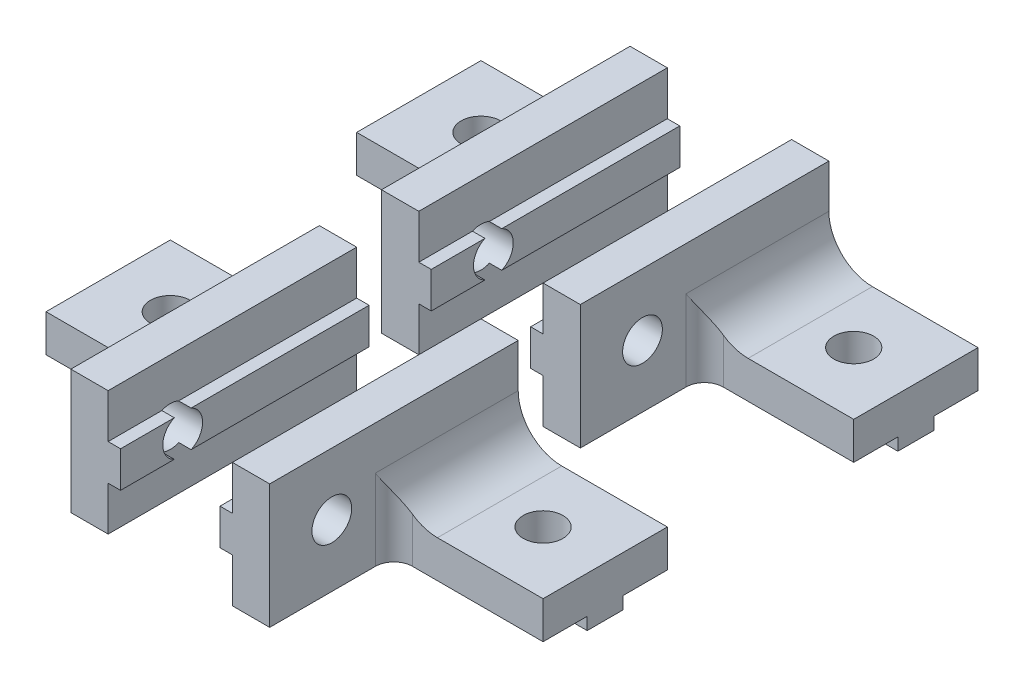
SolidWorks part; units mm, degrees
ref_plane "Front Plane" through (0, 0, 0) normal (0, 0, 1) x (1, 0, 0)
ref_plane "Top Plane" through (0, 0, 0) normal (0, 1, 0) x (1, 0, 0)
ref_plane "Right Plane" through (0, 0, 0) normal (1, 0, 0) x (0, 0, -1)
sketch "Esquisse1" plane through (0, 0, 0) normal (0, 0, 1) x (1, 0, 0)
  line L0 (0, 0) -> (15, 0)
  line L1 (15, 0) -> (15, 3)
  line L2 (15, 3) -> (6.5, 3)
  line L4 (3, 6.5) -> (3, 10)
  line L5 (3, 10) -> (0, 10)
  line L6 (0, 10) -> (0, 0)
  arc A0 (6.5, 3) -> (3, 6.5) centre (6.5, 6.5) cw
  dimension "D1" = 3.5
  dimension "D2" = 10
  dimension "D3" = 3
  dimension "D4" = 15
extrude "Main" add sketch "Esquisse1" along normal blind 20
sketch "Esquisse4" plane through (0, 0, 0) normal (-1, 0, 0) x (0, 0, 1)
  line L0 (20, 10) -> (0, 10) construction
  line L1 (0, 6.45) -> (20, 6.45)
  line L2 (0, 6.45) -> (0, 3.55)
  line L3 (0, 3.55) -> (20, 3.55)
  line L4 (20, 6.45) -> (20, 3.55)
  line L6 (0, 10) -> (0, 0) construction
  line L7 (20, 10) -> (20, 0) construction
  dimension "D1" = 2.9
  dimension "D2" = 3.55
extrude "VerticalGuidance" add sketch "Esquisse4" along normal blind 1
sketch "Esquisse2" plane through (0, 0, 0) normal (-1, 0, 0) x (0, 0, 1)
  line L4 (20, 6.5) -> (20, 10) construction
  line L5 (20, 0) -> (0, 0) construction
  circle A0 centre (15, 5) radius 1.6
  dimension "D1" = 3.2
  dimension "D2" = 5
  dimension "D3" = 5
extrude "VerticalHole" cut sketch "Esquisse2" against normal through all both and the other way through all
sketch "Esquisse5" plane through (0, 0, 0) normal (0, -1, 0) x (-1, 0, 0)
  line L1 (0, -3.55) -> (-15, -3.55)
  line L2 (0, -3.55) -> (0, -6.45)
  line L3 (0, -6.45) -> (-15, -6.45)
  line L4 (-15, -3.55) -> (-15, -6.45)
  line L8 (0, 0) -> (0, -14.3236) construction
  line L9 (-15, -20) -> (-15, 0) construction
  line L10 (0, 0) -> (-15, 0) construction
  dimension "D1" = 2.9
  dimension "D2" = 3.55
extrude "HorizontalGuidance" add sketch "Esquisse5" along normal blind 1
sketch "Esquisse3" plane through (0, 3, 0) normal (0, -1, 0) x (1, 0, 0)
  line L5 (15, 20) -> (15, 0) construction
  line L8 (15, 0) -> (6.5, 0) construction
  circle A0 centre (10, 5) radius 1.6
  dimension "D1" = 5
  dimension "D2" = 5
  dimension "D3" = 3.2
extrude "HorizontalHole" cut sketch "Esquisse3" against normal through all both and the other way through all
sketch "Esquisse9" plane through (0, 3, 0) normal (0, 1, 0) x (1, 0, 0)
  line L0 (15, -20) -> (15, 0) construction
  line L1 (3, -20) -> (15, -20)
  line L2 (3, -20) -> (3, -10)
  line L3 (3, -10) -> (15, -10)
  line L4 (15, -20) -> (15, -10)
  line L5 (15, 0) -> (6.5, 0) construction
  dimension "D1" = 10
extrude "Enlèv. mat.-Extru.4" cut sketch "Esquisse9" against normal through all both and the other way through all
fillet "Congé2" radius 1.5 1 edges at (3, 3.25, 10)
ref_plane "SymetryPlan" through (-5, 0, 0) normal (1, 0, 0) x (0, 0, -1)
ref_axis "Axe1" through (-5, 0, -4.75) along (0, 0, 1)
pattern_linear "Répétition linéaire1" count 2 spacing 25 along (0, 0, 1) of bodies 113 114
mirror "Symétrie3" about plane through (-5, 0, 0) normal (1, 0, 0) of bodies 115 113 116 117
